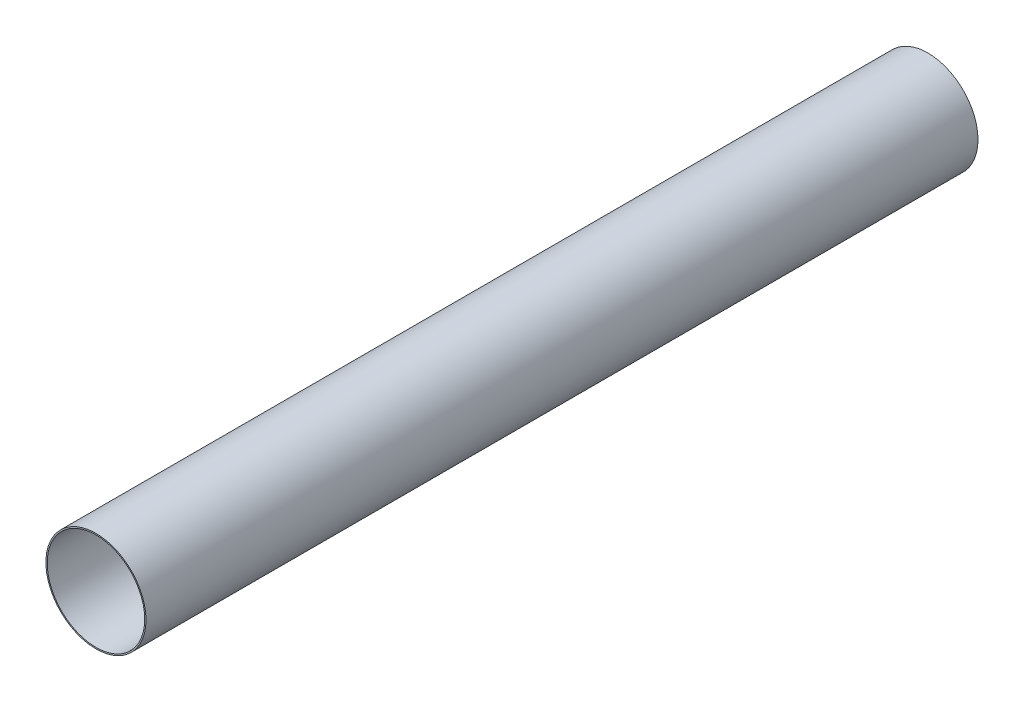
SolidWorks part; units mm, degrees
material "E-Glass Fiber"
ref_plane "Front" through (0, 0, 0) normal (0, 0, 1) x (1, 0, 0)
ref_plane "Top" through (0, 0, 0) normal (0, 1, 0) x (1, 0, 0)
ref_plane "Right" through (0, 0, 0) normal (1, 0, 0) x (0, 0, -1)
sketch "Sketch1" plane through (0, 0, 0) normal (0, 0, 1) x (1, 0, 0)
  circle A0 centre (0, 0) radius 78.2
  circle A1 centre (0, 0) radius 76.2
  dimension "D1" = 156.4
  dimension "D2" = 152.4
extrude "Boss-Extrude1" add sketch "Sketch1" along normal blind 1300
